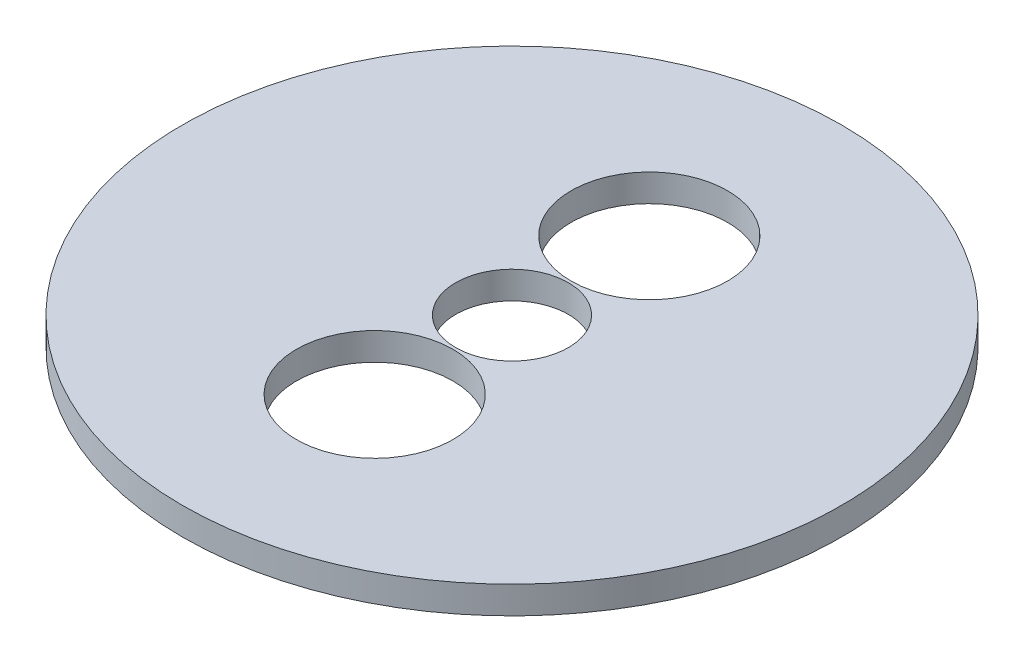
SolidWorks part; units mm, degrees
ref_plane "Front Plane" through (0, 0, 0) normal (0, 0, 1) x (1, 0, 0)
ref_plane "Top Plane" through (0, 0, 0) normal (0, 1, 0) x (1, 0, 0)
ref_plane "Right Plane" through (0, 0, 0) normal (1, 0, 0) x (0, 0, -1)
sketch "Sketch1" plane through (0, 0, 0) normal (0, 1, 0) x (1, 0, 0)
  line L0 (-55, 0) -> (55, 0) construction
  circle A0 centre (0, 0) radius 1200
  circle A1 centre (0, 0) radius 847.6 construction
  circle A2 centre (0, 500) radius 285
  circle A3 centre (0, 0) radius 205
  circle A4 centre (0, -500) radius 285
  circle A5 centre (0, 0) radius 785 construction
  dimension "D1" = 2400
  dimension "D2" = 1695.2
  dimension "D3" = 410
  dimension "D4" = 570
  dimension "D6" = 1570
  dimension "D5" = 500
extrude "Boss-Extrude1" add sketch "Sketch1" along normal blind 100
